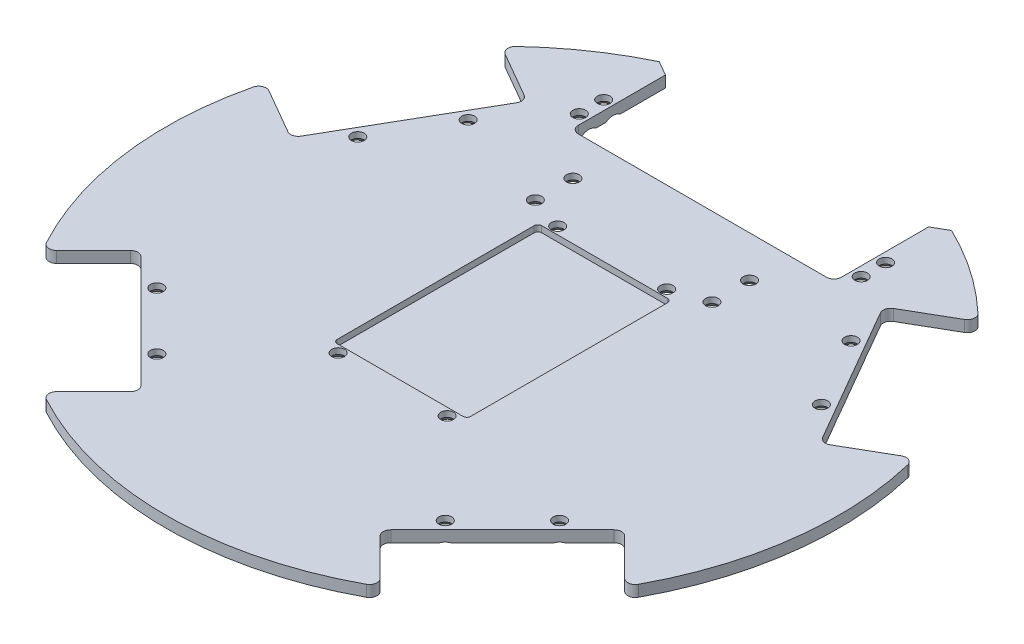
SolidWorks part; units mm, degrees
material "1.4301 (X5CrNi18-10)"
ref_plane "Front Plane" through (0, 0, 0) normal (0, 0, 1) x (1, 0, 0)
ref_plane "Top Plane" through (0, 0, 0) normal (0, 1, 0) x (1, 0, 0)
ref_plane "Right Plane" through (0, 0, 0) normal (1, 0, 0) x (0, 0, -1)
sketch "Sketch1" plane through (0, 0, 0) normal (0, 1, 0) x (1, 0, 0)
  circle A0 centre (0, 0) radius 90
  dimension "D1" = 180
extrude "Boss-Extrude1" add sketch "Sketch1" along normal blind 3
sketch "Sketch11" plane through (0, 3, 0) normal (0, 1, 0) x (1, 0, 0)
  line L0 (0, -1.7661) -> (0, 1.7661) construction
  line L1 (0, 0) -> (-77.9423, 45) construction
  line L2 (-1.7661, 0) -> (1.7661, 0) construction
  line L3 (0, 0) -> (63.6396, -63.6396) construction
  line L4 (0, 0) -> (-63.6396, -63.6396) construction
  line L5 (-64.3467, -31.8198) -> (-31.8198, -64.3467)
  line L6 (0, 0) -> (77.9423, 45) construction
  line L7 (31.8198, -64.3467) -> (45.263, -77.7899)
  line L8 (-47.3897, 53.9186) -> (-70.3897, 14.0814)
  line L9 (-70.3897, 14.0814) -> (-86.8542, 23.5872)
  line L10 (-47.3897, 53.9186) -> (-63.8542, 63.4243)
  line L11 (-64.3467, -31.8198) -> (-77.7899, -45.263)
  line L12 (-31.8198, -64.3467) -> (-45.263, -77.7899)
  line L14 (64.3467, -31.8198) -> (77.7899, -45.263)
  line L15 (47.3897, 53.9186) -> (63.8542, 63.4243)
  line L16 (70.3897, 14.0814) -> (86.8542, 23.5872)
  line L17 (47.3897, 53.9186) -> (70.3897, 14.0814)
  line L18 (64.3467, -31.8198) -> (31.8198, -64.3467)
  line L19 (0, 0) -> (0, 90) construction
  line L20 (35, 53.2) -> (-35, 53.2)
  line L21 (35, 53.2) -> (35, 82.9156)
  line L22 (-35, 53.2) -> (-35, 82.9156)
  circle A0 centre (0, 0) radius 90 construction
  arc A1 (-45.263, -77.7899) -> (-77.7899, -45.263) centre (0, 0) cw
  arc A2 (-63.8542, 63.4243) -> (-86.8542, 23.5872) centre (0, 0) ccw
  arc A3 (63.8542, 63.4243) -> (86.8542, 23.5872) centre (0, 0) cw
  arc A4 (45.263, -77.7899) -> (77.7899, -45.263) centre (0, 0) ccw
  arc A5 (35, 82.9156) -> (-35, 82.9156) centre (0, 0) ccw
  point P13 (-48.0833, -48.0833)
  point P22 (-58.8897, 34)
  point P34 (58.8897, 34)
  point P35 (48.0833, -48.0833)
  point P39 (0, 53.2)
  dimension "D1" = 30
  dimension "D4" = 22
  dimension "D5" = 46
  dimension "D6" = 22
  dimension "D7" = 46
  dimension "D2" = 45
  dimension "D3" = 36.8
  dimension "D8" = 70
extrude "Cut-Extrude2" cut sketch "Sketch11" against normal through all
hole_wizard "CSK for M3 Countersunk Flat Head Screw1" positions "Sketch12" profile "Sketch13" countersink size "M3" standard "ISO" end condition through all
sketch "Sketch12" plane through (0, 0, 0) normal (0, 1, 0) x (1, 0, 0)
  line L0 (-29.6985, -62.2254) -> (-62.2254, -29.6985) construction
  line L2 (-31.8198, -64.3467) -> (-64.3467, -31.8198) construction
  line L3 (-67.7917, 12.5814) -> (-44.7917, 52.4186) construction
  line L4 (-70.3897, 14.0814) -> (-47.3897, 53.9186) construction
  line L6 (-47.3897, 53.9186) -> (-44.7917, 52.4186) construction
  line L8 (-70.3897, 14.0814) -> (-67.7917, 12.5814) construction
  line L10 (-64.3467, -31.8198) -> (-62.2254, -29.6985) construction
  line L12 (-29.6985, -62.2254) -> (-31.8198, -64.3467) construction
  line L14 (0, -1.7661) -> (0, 1.7661) construction
  line L15 (29.6985, -62.2254) -> (31.8198, -64.3467) construction
  line L16 (64.3467, -31.8198) -> (62.2254, -29.6985) construction
  line L17 (70.3897, 14.0814) -> (67.7917, 12.5814) construction
  line L18 (47.3897, 53.9186) -> (44.7917, 52.4186) construction
  line L19 (67.7917, 12.5814) -> (44.7917, 52.4186) construction
  line L20 (29.6985, -62.2254) -> (62.2254, -29.6985) construction
  point P0 (-50.9167, 41.8098)
  point P2 (-61.6667, 23.1902)
  point P4 (-53.5633, -38.3605)
  point P6 (-38.3605, -53.5633)
  point P69 (38.3605, -53.5633)
  point P70 (53.5633, -38.3605)
  point P71 (61.6667, 23.1902)
  point P72 (50.9167, 41.8098)
  dimension "D1" = 3
  dimension "D2" = 3
  dimension "D3" = 21.5
  dimension "D4" = 21.5
  dimension "D5" = 12.25
  dimension "D6" = 12.25
sketch "Sketch13" plane through (-50.9167, 0, -41.8098) normal (1, 0, 0) x (0, 0, -1)
  line L0 (0, 0) -> (0, 3)
  line L1 (0, 3) -> (1.7, 3)
  line L2 (1.7, 3) -> (1.7, 1.45)
  line L3 (1.7, 1.45) -> (3.15, 0)
  line L5 (3.15, 0) -> (0, 0)
  line L6 (-1.7, 1.45) -> (-3.15, 0) construction
  line L11 (0, -6.35) -> (0, 107.95) construction
  dimension "Thru Hole Dia." = 3.4
  dimension "Thru Hole Depth" = 3
  dimension "Near C'Sink Dia." = 6.3
  dimension "Near C'Sink Angle" = 90
hole_wizard "CSK for M3 Countersunk Flat Head Screw2" positions "Sketch15" profile "Sketch16" countersink size "M3" standard "ISO" end condition through all
sketch "Sketch15" plane through (0, 0, 0) normal (0, -1, 0) x (-1, 0, 0)
  line L4 (0, 90) -> (0, -90) construction
  arc A0 (-35, 82.9156) -> (35, 82.9156) centre (0, 0) cw construction
  arc A1 (-35, 82.9156) -> (-63.8542, 63.4243) centre (0, 0) ccw construction
  arc A2 (-45.263, -77.7899) -> (45.263, -77.7899) centre (0, 0) ccw construction
  point P3 (14.5, 29.2)
  point P6 (14.5, -29.2)
  point P36 (0, 90)
  point P54 (-14.5, 29.2)
  point P55 (-14.5, -29.2)
  point P56 (-37.5, 57.95)
  point P58 (-37.5, 64.45)
  point P61 (37.5, 64.45)
  point P62 (37.5, 57.95)
  point P63 (-23.5, 42.25)
  point P65 (-23.5, 32.25)
  point P68 (23.5, 42.25)
  point P69 (23.5, 32.25)
  dimension "D3" = 60.8
  dimension "D4" = 14.5
  dimension "D1" = 58.4
  dimension "D2" = 37.5
  dimension "D5" = 6.5
  dimension "D6" = 28.75
  dimension "D7" = 10
  dimension "D8" = 23.5
  dimension "D9" = 13.05
sketch "Sketch16" plane through (-14.5, 0, -29.2) normal (1, 0, 0) x (0, 0, -1)
  line L0 (0, 0) -> (0, 3)
  line L1 (0, 3) -> (1.7, 3)
  line L2 (1.7, 3) -> (1.7, 1.45)
  line L3 (1.7, 1.45) -> (3.15, 0)
  line L5 (3.15, 0) -> (0, 0)
  line L6 (-1.7, 1.45) -> (-3.15, 0) construction
  line L11 (0, -6.35) -> (0, 107.95) construction
  dimension "Thru Hole Dia." = 3.4
  dimension "Thru Hole Depth" = 3
  dimension "Near C'Sink Dia." = 6.3
  dimension "Near C'Sink Angle" = 90
sketch "Sketch17" plane through (0, 3, 0) normal (0, -1, 0) x (1, 0, 0)
  line L0 (-12, -27.2) -> (12, -27.2)
  line L1 (-17.75, -24.7) -> (17.75, -24.7) construction
  line L2 (-17.75, -24.7) -> (-17.75, 24.7)
  line L3 (-17.75, 24.7) -> (17.75, 24.7) construction
  line L4 (17.75, -24.7) -> (17.75, 24.7)
  line L5 (-17.75, -24.7) -> (17.75, 24.7) construction
  line L6 (-17.75, 24.7) -> (17.75, -24.7) construction
  line L7 (12, -27.2) -> (12, -24.7) construction
  line L8 (12, -24.7) -> (17.75, -24.7) construction
  line L9 (-12, -27.2) -> (-12, -24.7) construction
  line L10 (-12, -24.7) -> (-17.75, -24.7) construction
  line L11 (-12, 27.2) -> (12, 27.2)
  line L12 (12, 27.2) -> (12, 24.7) construction
  line L13 (12, 24.7) -> (17.75, 24.7) construction
  line L14 (-12, 27.2) -> (-12, 24.7) construction
  line L15 (-12, 24.7) -> (-17.75, 24.7) construction
  line L16 (12, 27.2) -> (17.75, 27.2)
  line L17 (17.75, 27.2) -> (17.75, 24.7)
  line L18 (-12, 27.2) -> (-17.75, 27.2)
  line L19 (-17.75, 27.2) -> (-17.75, 24.7)
  line L20 (-12, -27.2) -> (-17.75, -27.2)
  line L21 (-17.75, -27.2) -> (-17.75, -24.7)
  line L22 (12, -27.2) -> (17.75, -27.2)
  line L23 (17.75, -27.2) -> (17.75, -24.7)
  circle A0 centre (-14.5, 29.2) radius 1.7 construction
  circle A1 centre (-14.5, 29.2) radius 1.7 construction
  point P0 (0, 0)
  point P10 (0, -27.2)
  point P15 (0, 27.2)
  point P18 (-14.875, 24.7)
  dimension "D1" = 35.5
  dimension "D2" = 14.5
  dimension "D5" = 2.5
  dimension "D6" = 24
  dimension "D4" = 54.4
  dimension "D3" = 2
extrude "Cut-Extrude3" cut sketch "Sketch17" along normal blind 1.65
sketch "Sketch18" plane through (0, 1.35, 0) normal (0, 1, 0) x (1, 0, 0)
  line L0 (17.75, -27.2) -> (-17.75, -27.2) construction
  line L1 (17.75, -24.7) -> (-17.75, -24.7)
  line L2 (17.75, -24.7) -> (17.75, 24.7)
  line L3 (17.75, 24.7) -> (-17.75, 24.7)
  line L4 (-17.75, -24.7) -> (-17.75, 24.7)
  line L5 (17.75, 27.2) -> (17.75, -27.2) construction
  line L8 (-17.75, -27.2) -> (-17.75, 27.2) construction
  line L9 (-17.75, 27.2) -> (17.75, 27.2) construction
  dimension "D1" = 2.5
  dimension "D2" = 2.5
sketch "Sketch19" plane through (0, 0, 0) normal (0, -1, 0) x (1, 0, 0)
  circle A0 centre (0, 0) radius 89.5
  circle A1 centre (0, 0) radius 90
  dimension "D1" = 179
extrude "Cut-Extrude4" cut sketch "Sketch19" against normal through all and the other way through all
fillet "Fillet2" radius 2 18 edges at (35, 1.5, -53.2) (-35, 1.5, -53.2) (-47.3897, 1.5, -53.9186) (-70.3897, 1.5, -14.0814) (-64.3467, 1.5, 31.8198) (-31.8198, 1.5, 64.3467) (31.8198, 1.5, 64.3467) (64.3467, 1.5, 31.8198) (70.3897, 1.5, -14.0814) (47.3897, 1.5, -53.9186) (-63.4062, 1.5, -63.1657) (-86.4062, 1.5, -23.3285) (-77.4241, 1.5, 44.8972) (-44.8972, 1.5, 77.4241) (44.8972, 1.5, 77.4241) (77.4241, 1.5, 44.8972) (63.4062, 1.5, -63.1657) (86.4062, 1.5, -23.3285)
chamfer "Chamfer1" distance 4 angle 60 2 edges at (-35, 1.5, -82.3726) (35, 1.5, -82.3726) first distance on face at (-35, 0.8935, -65.1485) first distance on face at (35, 0.8935, -65.1485)
fillet "Fillet3" radius 1 4 edges at (-17.75, 2.175, -27.2) (-17.75, 2.175, 27.2) (17.75, 2.175, 27.2) (17.75, 2.175, -27.2)
equation "\"Width_motorhole\"=46"
equation "\"D7@Sketch11\"=\"Width_motorhole\""
equation "\"D5@Sketch11\"=\"Width_motorhole\""
equation "\"Depth_motorhole\"= 22"
equation "\"D4@Sketch11\"=\"Depth_motorhole\""
equation "\"D6@Sketch11\"=\"Depth_motorhole\""
equation "\"Distance_Hole_Screw\"= 3"
equation "\"D2@Sketch12\"=\"Distance_Hole_Screw\""
equation "\"D1@Sketch12\"=\"Distance_Hole_Screw\""
equation "\"Distance_screws\"=21.5"
equation "\"D3@Sketch12\"=\"Distance_screws\""
equation "\"D4@Sketch12\"=\"Distance_screws\""
equation "\"D5@Sketch12\"=(\"Width_motorhole\"-\"Distance_screws\")/2"
equation "\"D6@Sketch12\"=(\"Width_motorhole\"-\"Distance_screws\")/2"
equation "\"Robot_Radius\"=180"
equation "\"D1@Sketch1\"=\"Robot_Radius\""
equation "\"Depth_fronthole\"= 36.8"
equation "\"D3@Sketch11\"=\"Depth_fronthole\""
equation "\"Width_fronthole\"= 70"
equation "\"D8@Sketch11\"=\"Width_fronthole\""
equation "\"Hole_space_solenoid\"= 29"
equation "\"Distance_hole_solenoid\"= 58.4"
equation "\"D4@Sketch15\"=\"Hole_space_solenoid\"/2"
equation "\"Width_solenoid_hole\"= 35.5"
equation "\"D1@Sketch17\"=\"Width_solenoid_hole\""
equation "\"D2@Sketch17\"=\"Hole_space_solenoid\"/2"
equation "\"Thickness_back_holder\"= 6"
equation "\"Distance_solenoid_holder\"=54.4"
equation "\"Distance_Screw_Solenoid_Front\"= 60.8"
equation "\"D3@Sketch15\"=\"Distance_Screw_Solenoid_Front\""
equation "\"D1@Sketch15\"=\"Distance_hole_solenoid\""
equation "\"D2@Sketch15\" = 75 / 2"
equation "\"W_Chipper\"= 52 - 5"
equation "\"D8@Sketch15\"=\"W_Chipper\"/2"
equation "\"D4@Sketch17\"=\"Distance_solenoid_holder\""
